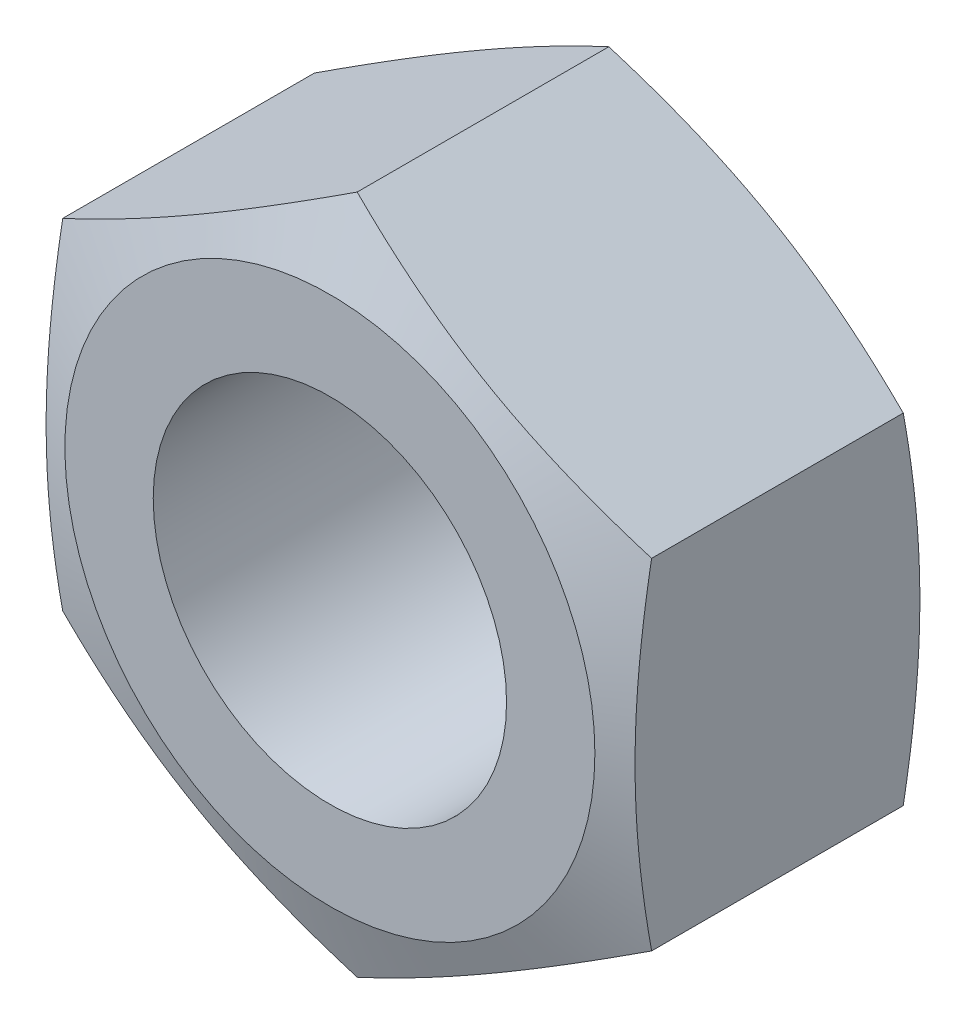
SolidWorks part; units mm, degrees
ref_plane "前视基准面" through (0, 0, 0) normal (0, 0, 1) x (1, 0, 0)
ref_plane "上视基准面" through (0, 0, 0) normal (0, 1, 0) x (1, 0, 0)
ref_plane "右视基准面" through (0, 0, 0) normal (1, 0, 0) x (0, 0, -1)
sketch "草图1" plane through (0, 0, 0) normal (0, 0, 1) x (1, 0, 0)
  line L1 (0, 5.7735) -> (-5, 2.8868)
  line L2 (-5, 2.8868) -> (-5, -2.8868)
  line L3 (-5, -2.8868) -> (0, -5.7735)
  line L4 (0, -5.7735) -> (5, -2.8868)
  line L5 (5, -2.8868) -> (5, 2.8868)
  line L6 (5, 2.8868) -> (0, 5.7735)
  circle A0 centre (0, 0) radius 5 construction
  dimension "s" = 10
extrude "凸台-拉伸1" add sketch "草图1" along normal blind 5.2
sketch "草图4" plane through (0, 0, 0) normal (1, 0, 0) x (0, 0, -1)
  line L0 (-5.2, -4.5) -> (-4.7365, -5.7735)
  line L1 (-5.2, -2.8868) -> (-5.2, -5.7735) construction
  line L2 (-5.2, -5.7735) -> (0, -5.7735) construction
  line L3 (-4.7365, -5.7735) -> (-5.2, -5.7735)
  line L4 (-5.2, -5.7735) -> (-5.2, -4.5)
  line L5 (-5.2, 0) -> (0, 0) construction
  line L6 (-5.2, 2.8868) -> (-5.2, -2.8868) construction
  line L7 (0, 2.8868) -> (0, -2.8868) construction
  dimension "D1" = 20
  dimension "D2" = 4.5
revolve "切除-旋转1" cut sketch "草图4" angle 360 about L5
ref_plane "基准面1" through (0, 0, 2.6) normal (0, 0, 1) x (1, 0, 0)
mirror "镜向1" about plane through (0, 0, 2.6) normal (0, 0, 1) of "切除-旋转1"
sketch "草图5" plane through (0, 0, 5.2) normal (0, 0, 1) x (1, 0, 0)
  circle A0 centre (0, 0) radius 3
  dimension "D1" = 6
extrude "切除-拉伸1" cut sketch "草图5" against normal through all
ref_axis "基准轴1" through (0, 0, 0) along (0, 0, 1)
ref_plane "基准面2" through (0, 0, 0) normal (0, 0, -1) x (-1, 0, 0)
ref_plane "基准面3" through (0, 0, 5.2) normal (0, 0, 1) x (1, 0, 0)
equation "\"D2@草图4\"= \"s@草图1\" * 0.45"
